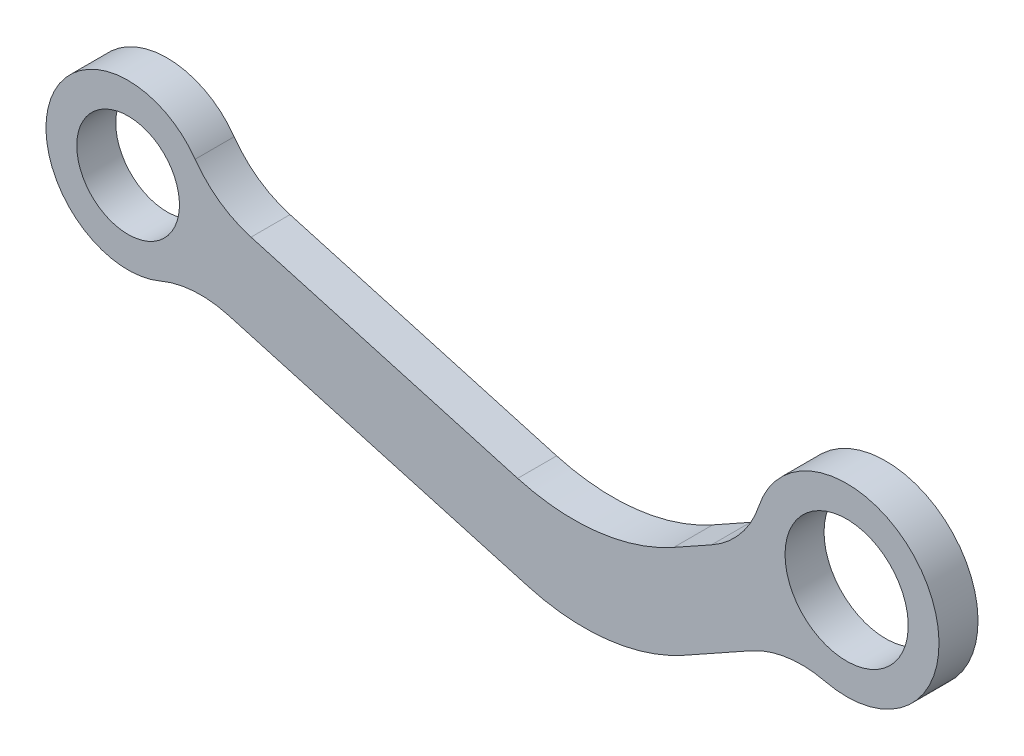
SolidWorks part; units mm, degrees
material "A2017"
ref_plane "正面" through (0, 0, 0) normal (0, 0, 1) x (1, 0, 0)
ref_plane "平面" through (0, 0, 0) normal (0, 1, 0) x (1, 0, 0)
ref_plane "右側面" through (0, 0, 0) normal (1, 0, 0) x (0, 0, -1)
sketch "ｽｹｯﾁ1" plane through (0, 0, 0) normal (0, 0, 1) x (1, 0, 0)
  line L0 (0, 0) -> (35, 0) construction
  circle A0 centre (0, 0) radius 2.5
  circle A1 centre (35, 0) radius 3
  circle A2 centre (35, 0) radius 4.5
  circle A3 centre (0, 0) radius 4
  dimension "D1" = 35
  dimension "D2" = 6
  dimension "D3" = 1.5
  dimension "D4" = 5
  dimension "D5" = 8
extrude "ﾎﾞｽ - 押し出し1" add sketch "ｽｹｯﾁ1" along normal blind 1.9
sketch "ｽｹｯﾁ3" plane through (0, 0, 1.9) normal (0, 0, 1) x (1, 0, 0)
  line L0 (35, 0) -> (23.2124, -6.5805) construction
  line L1 (23.2124, -6.5805) -> (0, 0) construction
  line L2 (30.5053, -0.2186) -> (22.9609, -4.4303)
  line L3 (22.9609, -4.4303) -> (3.8783, 0.9794)
  line L4 (32.4551, -3.7113) -> (23.4639, -8.7306)
  line L5 (23.4639, -8.7306) -> (2.7873, -2.869)
  line L7 (23.4639, -8.7306) -> (-0.5455, -1.9242) construction
  line L8 (22.9609, -4.4303) -> (0.5455, 1.9242) construction
  line L9 (34.0251, 1.7463) -> (22.9609, -4.4303) construction
  line L10 (35.9749, -1.7463) -> (23.4639, -8.7306) construction
  circle A2 centre (35, 0) radius 3 construction
  circle A3 centre (0, 0) radius 4 construction
  circle A4 centre (35, 0) radius 4.5 construction
  arc A5 (2.7873, -2.869) -> (3.8783, 0.9794) centre (0, 0) ccw
  arc A6 (30.5053, -0.2186) -> (32.4551, -3.7113) centre (35, 0) ccw
  point P1 (35, 0)
  dimension "D1" = 135
  dimension "D3" = 2
  dimension "D2" = 2
  dimension "D4" = 13.5
extrude "ﾎﾞｽ - 押し出し2" add sketch "ｽｹｯﾁ3" against normal up to surface (1.9 mm away) up to face at (4, 0, 0)
fillet "ﾌｨﾚｯﾄ1" radius 10 2 edges at (22.9609, -4.4303, 0.95) (23.4639, -8.7306, 0.95)
fillet "ﾌｨﾚｯﾄ2" radius 5 4 edges at (32.4551, -3.7113, 0.95) (30.5053, -0.2186, 0.95) (3.8783, 0.9794, 0.95) (2.7873, -2.869, 0.95)
